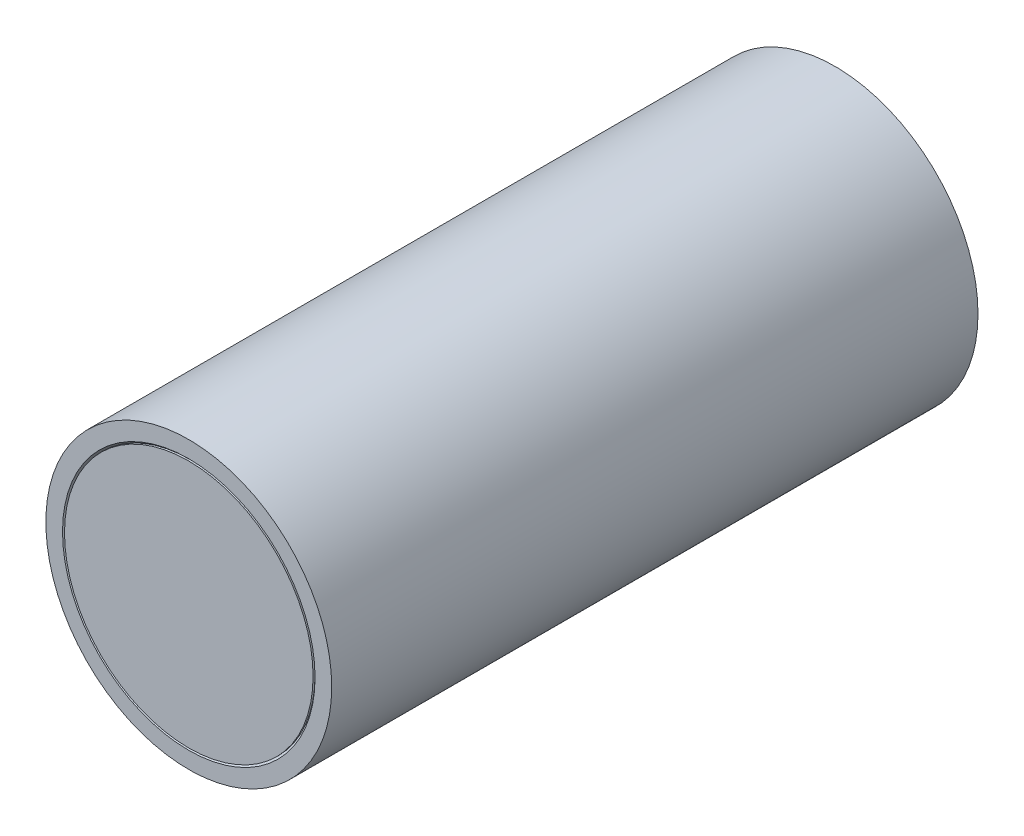
SolidWorks part; units mm, degrees
material "6061 Alloy"
ref_plane "Front Plane" through (0, 0, 0) normal (0, 0, 1) x (1, 0, 0)
ref_plane "Top Plane" through (0, 0, 0) normal (0, 1, 0) x (1, 0, 0)
ref_plane "Right Plane" through (0, 0, 0) normal (1, 0, 0) x (0, 0, -1)
sketch "Sketch1" plane through (0, 0, 0) normal (0, 0, 1) x (1, 0, 0)
  circle A0 centre (0, 0) radius 31.75
  circle A1 centre (0, 0) radius 36.5125
extrude "Extrude1" add sketch "Sketch1" along normal blind 165.1
sketch "Sketch2" plane through (0, 0, 0) normal (1, 0, 0) x (0, 0, -1)
  line L0 (-19.05, 36.5125) -> (-146.05, 36.5125)
  line L1 (0, 36.5125) -> (-165.1, 36.5125) construction
  line L2 (-146.05, 36.5125) -> (-144.4625, 34.925)
  line L3 (-144.4625, 34.925) -> (-20.6375, 34.925)
  line L4 (-20.6375, 34.925) -> (-19.05, 36.5125)
  line L5 (0, 0) -> (-165.1, 0) construction
  line L6 (-165.1, 36.5125) -> (-165.1, -36.5125) construction
  dimension "D1" = 1.5875
  dimension "D2" = 19.05
  dimension "D3" = 19.05
  dimension "D4" = 20.6375
  dimension "D5" = 20.6375
sketch "Sketch3" plane through (0, 0, 0) normal (1, 0, 0) x (0, 0, -1)
  line L1 (-101.6, 6.35) -> (-82.55, 6.35)
  line L2 (-101.6, 6.35) -> (-101.6, -6.35)
  line L3 (-101.6, -6.35) -> (-82.55, -6.35)
  line L4 (-82.55, 6.35) -> (-82.55, -6.35)
  line L7 (-19.05, 6.35) -> (0, 6.35)
  line L8 (-19.05, 6.35) -> (-19.05, -6.35)
  line L9 (-19.05, -6.35) -> (0, -6.35)
  line L10 (0, 6.35) -> (0, -6.35)
  circle A0 centre (-92.075, 0) radius 1.778
  circle A1 centre (-9.525, 0) radius 1.778
  dimension "D4" = 9.525
  dimension "D1" = 12.7
  dimension "D2" = 12.7
  dimension "D3" = 6.35
  dimension "D5" = 9.525
  dimension "D6" = 19.05
  dimension "D7" = 19.05
  dimension "D8" = 63.5
chamfer "Chamfer1" distance 0.508 angle 45 2 edges at (31.75, 0, 165.1) (31.75, 0, 0)
extrude "Boss-Extrude1" add sketch "Sketch1<2>" along normal blind 165.1 separate body contours A0
sketch "Sketch1<2>" plane through (0, 0, 0) normal (0, 0, 1) x (1, 0, 0) same geometry as "Sketch1"
